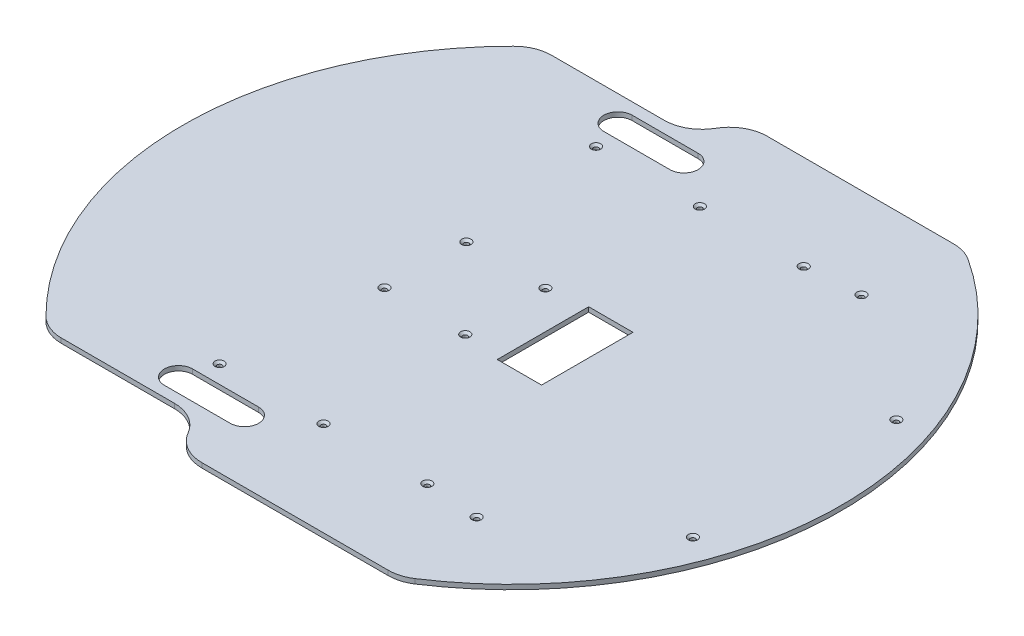
SolidWorks part; units mm, degrees
ref_plane "Plan de face" through (0, 0, 0) normal (0, 0, 1) x (1, 0, 0)
ref_plane "Plan de dessus" through (0, 0, 0) normal (0, 1, 0) x (1, 0, 0)
ref_plane "Plan de droite" through (0, 0, 0) normal (1, 0, 0) x (0, 0, -1)
sketch "Esquisse1" plane through (0, 0, 0) normal (0, 1, 0) x (1, 0, 0)
  line L0 (-138.94, 165.455) -> (-62.65, 165.455)
  line L5 (106.95, -190.145) -> (-18.65, -190.145)
  line L7 (-18.65, 190.855) -> (106.95, 190.855)
  line L8 (-138.94, -164.745) -> (-62.65, -164.745)
  arc A1 (-156.83, 157.725) -> (-138.94, 165.455) centre (-138.5811, 140.0575) cw
  arc A2 (-62.65, 165.455) -> (-40.65, 178.155) centre (-62.647, 190.855) ccw
  arc A3 (-40.65, 178.155) -> (-18.65, 190.855) centre (-18.653, 165.455) cw
  arc A4 (106.95, 190.855) -> (120.78, 186.755) centre (106.9427, 165.455) cw
  arc A5 (120.78, 186.755) -> (120.78, -186.045) centre (-0.716, 0.355) cw
  arc A6 (120.78, -186.045) -> (106.95, -190.145) centre (106.9427, -164.745) cw
  arc A7 (-18.65, -190.145) -> (-40.65, -177.445) centre (-18.653, -164.745) cw
  arc A8 (-40.65, -177.445) -> (-62.65, -164.745) centre (-62.647, -190.145) ccw
  arc A9 (-156.83, -157.015) -> (-138.94, -164.745) centre (-138.5811, -139.3475) ccw
  arc A10 (-156.83, 157.725) -> (-156.83, -157.015) centre (0.4625, 0.355) ccw
  point P0 (0, 0)
  dimension "D3" = 222.5
  dimension "D5" = 25.4
  dimension "D7" = 25.4
  dimension "D9" = 25.4
  dimension "D12" = 25.4
  dimension "D14" = 222.5
  dimension "D15" = 25.4
  dimension "D18" = 25.4
  dimension "D19" = 76.29
  dimension "D21" = 25.4
  dimension "D22" = 25.4
  dimension "D2" = 125.6
  dimension "D4" = 157.725
  dimension "D6" = 76.29
  dimension "D8" = 22
  dimension "D10" = 22
  dimension "D11" = 125.6
  dimension "D13" = 4.1
  dimension "D16" = 4.1
  dimension "D17" = 13.83
  dimension "D20" = 22
  dimension "D23" = 381
  dimension "D24" = 277.61
  dimension "D25" = 330.2
  dimension "D26" = 22
  dimension "D27" = 17.89
  dimension "D28" = 17.89
  dimension "D29" = 7.73
  dimension "D30" = 7.73
  dimension "D31" = 25.4
  dimension "D32" = 156.83
extrude "Boss.-Extru.1" add sketch "Esquisse1" along normal blind 3.18
sketch "Esquisse2" plane through (0, 3.18, 0) normal (0, 1, 0) x (1, 0, 0)
  line L0 (-76.45, -148.105) -> (-32, -148.105) construction
  line L1 (-76.45, -138.575) -> (-32, -138.575)
  line L2 (-76.45, -157.635) -> (-32, -157.635)
  line L3 (-138.94, -164.745) -> (-62.65, -164.745) construction
  line L4 (0, 0) -> (-294.8551, 0) construction
  line L5 (-76.45, 148.105) -> (-32, 148.105) construction
  line L6 (-76.45, 138.575) -> (-32, 138.575)
  line L7 (-76.45, 157.635) -> (-32, 157.635)
  line L8 (20.7, -30.425) -> (50.55, -30.425)
  line L9 (20.7, -30.425) -> (20.7, 31.175)
  line L10 (20.7, 31.175) -> (50.55, 31.175)
  line L11 (50.55, -30.425) -> (50.55, 31.175)
  arc A0 (-76.45, -138.575) -> (-76.45, -157.635) centre (-76.45, -148.105) ccw
  arc A1 (-32, -157.635) -> (-32, -138.575) centre (-32, -148.105) ccw
  arc A2 (-76.45, 138.575) -> (-76.45, 157.635) centre (-76.45, 148.105) cw
  arc A3 (-32, 157.635) -> (-32, 138.575) centre (-32, 148.105) cw
  point P2 (-54.225, -148.105)
  point P15 (-54.225, 148.105)
  dimension "D1" = 9.53
  dimension "D2" = 7.11
  dimension "D3" = 13.8
  dimension "D4" = 44.45
  dimension "D5" = 61.6
  dimension "D6" = 159.64
  dimension "D7" = 134.32
  dimension "D8" = 29.85
extrude "Enlèv. mat.-Extru.1" cut sketch "Esquisse2" against normal blind 3.18
sketch "Esquisse3" plane through (0, 3.18, 0) normal (0, 1, 0) x (1, 0, 0)
  line L1 (0.4625, 0.355) -> (-274.8168, 0.355) construction
  point P0 (-70.35, -126.475)
  point P1 (-0.37, -126.475)
  point P3 (69.61, -126.475)
  point P5 (105.7, -129.345)
  point P8 (190.32, -68.205)
  point P10 (190.32, 68.915)
  point P11 (105.7, 130.055)
  point P12 (69.61, 127.185)
  point P13 (-0.37, 127.185)
  point P14 (-70.35, 127.185)
  dimension "D1" = 12.1
  dimension "D2" = 6.1
  dimension "D3" = 69.98
  dimension "D4" = 69.98
  dimension "D5" = 2.87
  dimension "D6" = 36.09
  dimension "D7" = 84.62
  dimension "D8" = 61.14
hole_wizard "Fraisage pour vis à tête fraisée M31" positions "Esquisse3D2" profile "Esquisse8" countersink size "M3" standard "Ansi Metric" end condition through all
sketch3d "Esquisse3D2"
  point P0 (-70.35, 3.18, 126.475)
  point P3 (-0.37, 3.18, 126.475)
  point P6 (69.61, 3.18, 126.475)
  point P9 (105.7, 3.18, 129.345)
  point P12 (190.32, 3.18, 68.205)
  point P15 (190.32, 3.18, -68.915)
  point P18 (105.7, 3.18, -130.055)
  point P21 (69.61, 3.18, -127.185)
  point P24 (-0.37, 3.18, -127.185)
  point P27 (-70.35, 3.18, -127.185)
sketch "Esquisse8" plane through (-70.35, 3.18, 126.475) normal (1, 0, 0) x (0, 0, 1)
  line L0 (0, 0) -> (0, 3.18)
  line L1 (0, 3.18) -> (1.7, 3.18)
  line L2 (1.7, 3.18) -> (1.7, 1.45)
  line L3 (1.7, 1.45) -> (3.15, 0)
  line L5 (3.15, 0) -> (0, 0)
  line L6 (-1.7, 1.45) -> (-3.15, 0) construction
  line L11 (0, -6.35) -> (0, 107.95) construction
  dimension "Diamètre du perçage jusqu'au prochain" = 3.4
  dimension "Profondeur du perçage jusqu'au prochain" = 3.18
  dimension "Diamètre du fraisage entrant" = 6.3
  dimension "Angle du fraisage entrant" = 90
sketch "Esquisse9" plane through (0, 3.18, 0) normal (0, 1, 0) x (1, 0, 0)
  line L0 (20.7, 31.175) -> (20.7, -30.425) construction
  line L1 (-129.4413, 0.355) -> (65.4144, -112.145) construction
  line L2 (65.4144, -112.145) -> (65.4144, 112.855) construction
  line L3 (65.4144, 112.855) -> (-129.4413, 0.355) construction
  line L13 (-4.72, 27.445) -> (-4.72, -26.555) construction
  line L14 (-4.72, -26.555) -> (-59.23, -26.5244) construction
  line L15 (-59.23, -26.5244) -> (-58.3786, 27.829) construction
  line L16 (-58.3786, 27.829) -> (-4.72, 27.445) construction
  circle A0 centre (0.4625, 0.355) radius 64.9519 construction
  dimension "D2" = 54.36
  dimension "D1" = 225
  dimension "D3" = 54
  dimension "D4" = 3.73
  dimension "D5" = 25.42
  dimension "D6" = 53.66
  dimension "D7" = 54.51
  dimension "D8" = 90.41
  dimension "D9" = 90.487
hole_wizard "Fraisage pour vis à tête fraisée M32" positions "Esquisse3D3" profile "Esquisse10" countersink size "M3" standard "Ansi Metric" end condition through all
sketch3d "Esquisse3D3"
  point P0 (-59.23, 3.18, 26.5244)
  point P3 (-58.3786, 3.18, -27.829)
  point P6 (-4.72, 3.18, -27.445)
  point P9 (-4.72, 3.18, 26.555)
sketch "Esquisse10" plane through (-59.23, 3.18, 26.5244) normal (1, 0, 0) x (0, 0, 1)
  line L0 (0, 0) -> (0, 3.18)
  line L1 (0, 3.18) -> (1.7, 3.18)
  line L2 (1.7, 3.18) -> (1.7, 1.45)
  line L3 (1.7, 1.45) -> (3.15, 0)
  line L5 (3.15, 0) -> (0, 0)
  line L6 (-1.7, 1.45) -> (-3.15, 0) construction
  line L11 (0, -6.35) -> (0, 107.95) construction
  dimension "Diamètre du perçage jusqu'au prochain" = 3.4
  dimension "Profondeur du perçage jusqu'au prochain" = 3.18
  dimension "Diamètre du fraisage entrant" = 6.3
  dimension "Angle du fraisage entrant" = 90
